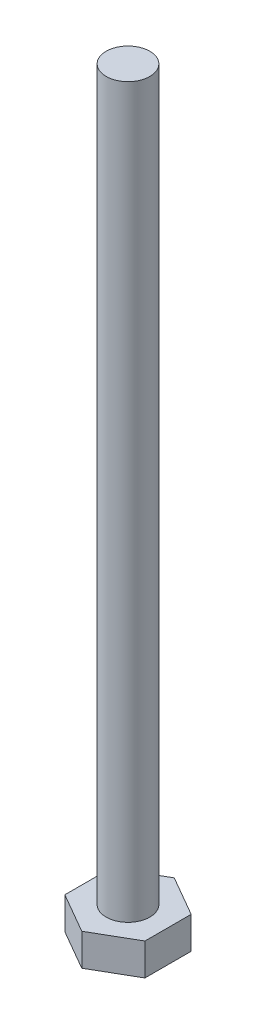
SolidWorks part; units mm, degrees
ref_plane "前视基准面" through (0, 0, 0) normal (0, 0, 1) x (1, 0, 0)
ref_plane "上视基准面" through (0, 0, 0) normal (0, 1, 0) x (1, 0, 0)
ref_plane "右视基准面" through (0, 0, 0) normal (1, 0, 0) x (0, 0, -1)
sketch "草图1" plane through (0, 0, 0) normal (0, 1, 0) x (1, 0, 0)
  line L1 (0, -3.1754) -> (2.75, -1.5877)
  line L2 (2.75, -1.5877) -> (2.75, 1.5877)
  line L3 (2.75, 1.5877) -> (0, 3.1754)
  line L4 (0, 3.1754) -> (-2.75, 1.5877)
  line L5 (-2.75, 1.5877) -> (-2.75, -1.5877)
  line L6 (-2.75, -1.5877) -> (0, -3.1754)
  circle A0 centre (0, 0) radius 2.75 construction
  circle A1 centre (0, 0) radius 1.5
  dimension "D1" = 5.5
extrude "凸台-拉伸3" add sketch "草图1" along normal blind 50 contours A1 region at (0, 0, 0)
extrude "凸台-拉伸4" add sketch "草图1<4>" against normal blind 2.2 contours L5 L6 L1 L2 L3 L4 A1 | A1 region at (-1.333, 0, 2.3088) region at (0, 0, 0)
sketch "草图1<4>" plane through (0, 0, 0) normal (0, 1, 0) x (1, 0, 0) same geometry as "草图1"
